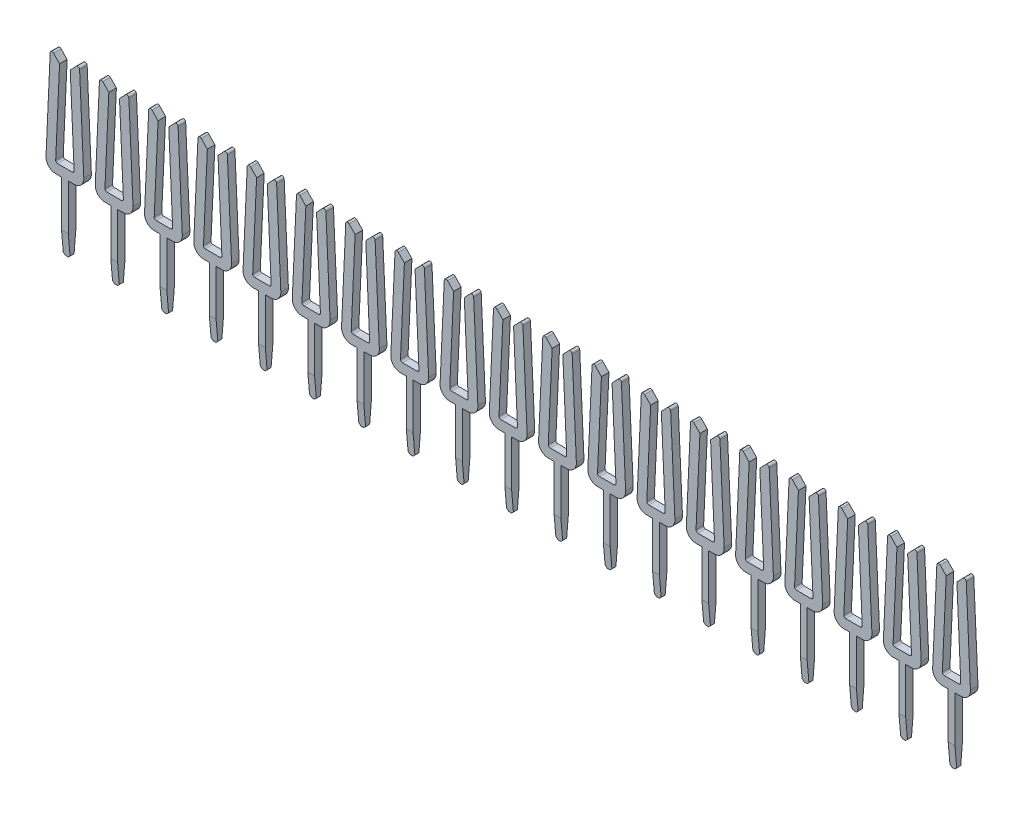
SolidWorks part; units mm, degrees
other "Шпилька"
ref_plane "Front Plane" through (0, 0, 0) normal (0, 0, 1) x (1, 0, 0)
ref_plane "Top Plane" through (0, 0, 0) normal (0, 1, 0) x (1, 0, 0)
ref_plane "Right Plane" through (0, 0, 0) normal (1, 0, 0) x (0, 0, -1)
sketch "Эскиз-Шпилька" plane through (0, 0, 0) normal (0, 0, 1) x (1, 0, 0)
  line L0 (-0.2751, 4.5045) -> (-0.586, 4.8299)
  line L1 (-0.7582, 4.7653) -> (-0.9745, 0.0228)
  line L2 (-0.475, -0.5) -> (-0.175, -0.5)
  line L3 (-0.175, -0.5) -> (-0.175, -3.9)
  line L4 (-0.175, -3.9) -> (-0.075, -4)
  line L5 (0, 4.5045) -> (0, -4) construction
  line L6 (-0.375, 0) -> (0.375, 0)
  line L7 (-0.4749, 0.1045) -> (-0.2751, 4.5045)
  line L8 (0.4749, 0.1045) -> (0.2751, 4.5045)
  line L9 (0.175, -3.9) -> (0.075, -4)
  line L10 (0.175, -0.5) -> (0.175, -3.9)
  line L11 (0.475, -0.5) -> (0.175, -0.5)
  line L12 (0.7582, 4.7653) -> (0.9745, 0.0228)
  line L13 (0.2751, 4.5045) -> (0.586, 4.8299)
  line L14 (-0.075, -4) -> (0.075, -4)
  arc A0 (-0.9745, 0.0228) -> (-0.475, -0.5) centre (-0.475, 0) ccw
  arc A1 (-0.4749, 0.1045) -> (-0.375, 0) centre (-0.375, 0.1) ccw
  arc A2 (-0.586, 4.8299) -> (-0.7582, 4.7653) centre (-0.6583, 4.7608) ccw
  arc A3 (0.586, 4.8299) -> (0.7582, 4.7653) centre (0.6583, 4.7608) cw
  arc A4 (0.4749, 0.1045) -> (0.375, 0) centre (0.375, 0.1) cw
  arc A5 (0.9745, 0.0228) -> (0.475, -0.5) centre (0.475, 0) cw
  point P26 (0, 0)
  dimension "D1" = 2.6
  dimension "D2" = 0.1
  dimension "D6" = 0.1
  dimension "D8" = 0.5
  dimension "D3" = 0.45
  dimension "D4" = 133.7
  dimension "D5" = 4.4
  dimension "D7" = 0.375
  dimension "D9" = 0.3
  dimension "D10" = 3.5
  dimension "D11" = 0.1
  dimension "D12" = 0.1
  dimension "D13" = 0.35
  dimension "D14" = 0.5
extrude "Бобышка-Шпилька" add sketch "Эскиз-Шпилька" along normal blind 0.195 and the other way blind 0.195
chamfer "Фаска1" distance 0.1 angle 85 1 edges at (0, -4, 0.195) first distance on face at (0, -4, 0)
chamfer "Фаска2" distance 0.1 angle 85 1 edges at (0, -4, -0.195) first distance on face at (0, -4, -0.05)
pattern_linear "Линейный массив1" count 19 spacing 2.54 along (-1, 0, 0) of "Бобышка-Шпилька"
